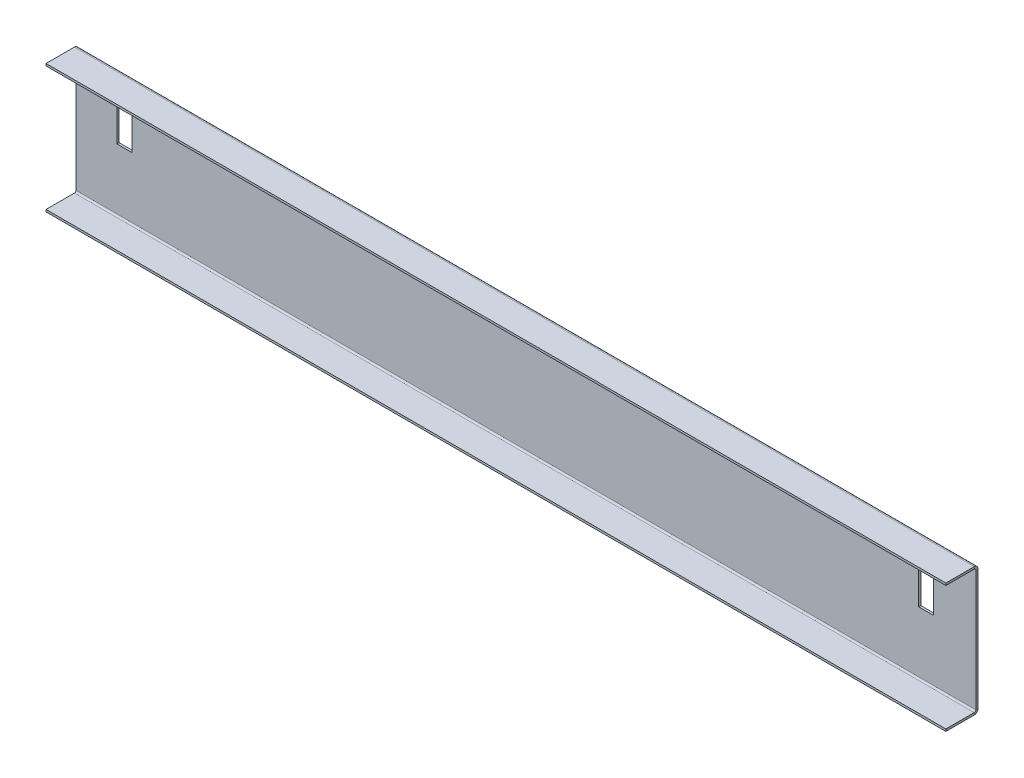
SolidWorks part; units mm, degrees
note: The reader was unsure of these and kept them because the rebuilt part matched: thickness of "Base-Flange1", "Edge-Flange1", "Edge-Flange2", "Sheet-Metal1", "Sheet-Metal2", "Sheet-Metal3", "Sheet-Metal4"; flange length of "Edge-Flange1", "Edge-Flange2".
ref_plane "Front Plane" through (0, 0, 0) normal (0, 0, 1) x (1, 0, 0)
ref_plane "Top Plane" through (0, 0, 0) normal (0, 1, 0) x (1, 0, 0)
ref_plane "Right Plane" through (0, 0, 0) normal (1, 0, 0) x (0, 0, -1)
sketch "Sketch1" plane through (0, 0, 0) normal (0, 0, 1) x (1, 0, 0)
  line L0 (0, 61.3529) -> (0, -66.9118) construction
  line L9 (-200.855, 38.7059) -> (-193.855, 38.7059) construction
  line L10 (-200.855, 38.7059) -> (-200.855, 26.7059) construction
  line L11 (-200.855, 26.7059) -> (-193.855, 26.7059) construction
  line L12 (-193.855, 38.7059) -> (-193.855, 26.7059) construction
  line L13 (-200.855, 38.7059) -> (-193.855, 26.7059) construction
  line L14 (-200.855, 26.7059) -> (-193.855, 38.7059) construction
  line L15 (-200.855, -471.2941) -> (-193.855, -471.2941) construction
  line L16 (-200.855, -471.2941) -> (-200.855, -483.2941) construction
  line L17 (-200.855, -483.2941) -> (-193.855, -483.2941) construction
  line L18 (-193.855, -471.2941) -> (-193.855, -483.2941) construction
  line L19 (-200.855, -471.2941) -> (-193.855, -483.2941) construction
  line L20 (-200.855, -483.2941) -> (-193.855, -471.2941) construction
  line L21 (200.855, -483.2941) -> (193.855, -483.2941) construction
  line L22 (193.855, -471.2941) -> (193.855, -483.2941) construction
  line L23 (200.855, -471.2941) -> (193.855, -471.2941) construction
  line L24 (200.855, -471.2941) -> (200.855, -483.2941) construction
  line L25 (200.855, 26.7059) -> (193.855, 26.7059) construction
  line L26 (193.855, 38.7059) -> (193.855, 26.7059) construction
  line L27 (200.855, 38.7059) -> (193.855, 38.7059) construction
  line L28 (200.855, 38.7059) -> (200.855, 26.7059) construction
  line L29 (-197.355, 38.7059) -> (-197.355, 18.7059) construction
  line L30 (-210, 48.7059) -> (210, 48.7059)
  line L34 (-210, 48.7059) -> (-210, -11.2941)
  line L35 (210, -11.2941) -> (210, 48.7059)
  line L36 (-200.855, 26.7059) -> (-193.855, 26.7059) construction
  line L37 (-200.855, 26.7059) -> (-200.855, 18.7059) construction
  line L38 (-200.855, 18.7059) -> (-193.855, 18.7059) construction
  line L39 (-193.855, 26.7059) -> (-193.855, 18.7059) construction
  line L40 (193.855, 26.7059) -> (200.855, 26.7059) construction
  line L41 (193.855, 26.7059) -> (193.855, 18.7059) construction
  line L42 (193.855, 18.7059) -> (200.855, 18.7059) construction
  line L43 (200.855, 26.7059) -> (200.855, 18.7059) construction
  line L47 (-210, -11.2941) -> (210, -11.2941)
  point P0 (-197.355, 32.7059)
  point P5 (-197.355, -477.2941)
  point P17 (-197.355, 28.7059)
  point P24 (0, 28.7059)
  dimension "D1" = 7
  dimension "D2" = 7
  dimension "D3" = 12
  dimension "D4" = 12
  dimension "D5" = 197.355
  dimension "D6" = 510
  dimension "D7" = 210
  dimension "D8" = 420
  dimension "D9" = 20
  dimension "D10" = 20
  dimension "D11" = 60
  dimension "D12" = 20
base flange "Base-Flange1" sketch "Sketch1" thickness 1 reverse thickness direction no parameters "D1"=0.7366
edge flange "Edge-Flange1" sketch "Sketch8" flange angle 90 flange length 15 flange position material inside bend radius 0.7366 thickness 1 relief rectangular parameters "D6"=10
sketch "Sketch8" plane through (0, 48.7059, 0) normal (0, 1, 0) x (-1, 0, 0)
  line L2 (-210, 0) -> (-210, 14)
  line L3 (-210, 14) -> (210, 14)
  line L4 (210, 14) -> (210, 0)
  line L7 (-210, 0) -> (210, 0) construction
  line L8 (-210, 0) -> (210, 0)
bend "EdgeBend1" bend radius 0.7366 bend angle 90 parameters "D5"=1
edge flange "Edge-Flange2" sketch "Sketch14" flange angle 90 flange length 15 flange position material inside bend radius 0.7366 thickness 1 relief rectangular parameters "D6"=10
bend "EdgeBend3" bend radius 0.7366 bend angle 90 parameters "D5"=2
sketch "Sketch14" plane through (0, -11.2941, 0) normal (0, -1, 0) x (1, 0, 0)
  line L0 (-210, 0) -> (210, 0) construction
  line L1 (-210, 0) -> (210, 0)
  line L2 (-210, 0) -> (-210, 14)
  line L3 (-210, 14) -> (210, 14)
  line L4 (210, 14) -> (210, 0)
sketch "Sketch15" plane through (0, 0, 0) normal (0, 0, 1) x (1, 0, 0)
  line L1 (189.818, 8.75) -> (183.818, 8.75)
  line L2 (189.818, 8.75) -> (189.818, 22.75)
  line L3 (189.818, 22.75) -> (183.818, 22.75)
  line L4 (183.818, 8.75) -> (183.818, 22.75)
sketch "Sketch12" plane through (0, 0, 0) normal (0, 0, 1) x (1, 0, 0)
  line L0 (0, 74.6372) -> (0, -36.0253) construction
  line L1 (-190.855, 38.75) -> (-183.855, 38.75)
  line L2 (-190.855, 38.75) -> (-190.855, 18.75)
  line L4 (-183.855, 38.75) -> (-183.855, 18.75)
  line L9 (-183.855, 28.75) -> (183.855, 28.75) construction
  line L11 (-190.855, 38.75) -> (-190.855, 18.75)
  line L12 (-190.855, 18.75) -> (-183.855, 18.75)
  line L13 (-183.855, 38.75) -> (-183.855, 18.75)
  line L15 (183.318, 38.75) -> (190.318, 38.75)
  line L16 (183.318, 38.75) -> (183.318, 18.75)
  line L17 (183.318, 18.75) -> (190.318, 18.75)
  line L18 (190.318, 38.75) -> (190.318, 18.75)
  line L19 (183.318, 38.75) -> (190.318, 18.75) construction
  line L20 (183.318, 18.75) -> (190.318, 38.75) construction
  point P4 (186.818, 28.75)
  dimension "D1" = 20
  dimension "D2" = 7
  dimension "D3" = 183.855
  dimension "D4" = 20
  dimension "D5" = 18.75
  dimension "D6" = 7
extrude "Cut-Extrude1" cut sketch "Sketch12" against normal through all contours L18 L15 L16 L17 | L2 L12 L4 L1 normal cut yes
sketch "Bend-Lines1" [suppressed] plane through (0, 0, 0) normal (0, 1, 0) x (1, 0, 0)
sketch "Bounding-Box1" [suppressed] plane through (0, 0, 0) normal (0, 1, 0) x (1, 0, 0)
sheet metal parameters "Sheet-Metal1" thickness 1 parameters "D1"=0.7366
flat pattern "Flat-Pattern1" [suppressed]
sketch "Bend-Lines2" plane through (0, 0, 0) normal (0, 1, 0) x (1, 0, 0)
sketch3d "Bounding-Box2" [suppressed]
  line L0 (225, 12.7059, 0) -> (-225, 12.7059, 0) construction
  line L1 (225, 52.7059, 0) -> (-225, 52.7059, 0) construction
  line L2 (225, 12.7059, 0) -> (225, 52.7059, 0) construction
  line L3 (-225, 12.7059, 0) -> (-225, 52.7059, 0) construction
sheet metal parameters "Sheet-Metal2" thickness 1 parameters "D1"=0.7366, "D7"=2
flat pattern "Flat-Pattern1"
sketch "Bend-Lines2" plane through (0, 0, 0) normal (0, 0, 1) x (1, 0, 0)
  line L0 (225, 51.3332) -> (-225, 51.3332) construction
  line L1 (225, 51.3332) -> (-225, 51.3332) construction
sketch3d "Bounding-Box2" [suppressed]
  line L0 (-225, 12.7059, 0) -> (225, 12.7059, 0) construction
  line L1 (-225, 64.9605, 0) -> (225, 64.9605, 0) construction
  line L2 (-225, 12.7059, 0) -> (-225, 64.9605, 0) construction
  line L3 (225, 12.7059, 0) -> (225, 64.9605, 0) construction
bend of the flat pattern "Flatten-<EdgeBend1>1"
sheet metal parameters "Sheet-Metal3" thickness 1 parameters "D1"=0.7366, "D7"=2
flat pattern "Flat-Pattern1" [suppressed]
sketch "Bend-Lines2" plane through (0, 0, 0) normal (0, 0, 1) x (1, 0, 0)
  line L0 (225, 51.3332) -> (-225, 51.3332) construction
  line L1 (225, 51.3332) -> (-225, 51.3332) construction
  line L2 (-225, 14.0786) -> (225, 14.0786) construction
  line L3 (-225, 14.0786) -> (225, 14.0786) construction
sketch3d "Bounding-Box2" [suppressed]
  line L0 (-225, 0.4512, 0) -> (225, 0.4512, 0) construction
  line L1 (-225, 64.9605, 0) -> (225, 64.9605, 0) construction
  line L2 (-225, 0.4512, 0) -> (-225, 64.9605, 0) construction
  line L3 (225, 0.4512, 0) -> (225, 64.9605, 0) construction
bend of the flat pattern "Flatten-<EdgeBend1>1"
bend of the flat pattern "Flatten-<EdgeBend3>1"
sheet metal parameters "Sheet-Metal4" thickness 1 parameters "D1"=0.7366, "D7"=2
flat pattern "Flat-Pattern1"
sketch "Bend-Lines2" plane through (0, 0, 0) normal (0, 0, 1) x (1, 0, 0)
  line L0 (210, 47.9405) -> (-210, 47.9405) construction
  line L1 (210, 47.9405) -> (-210, 47.9405) construction
  line L2 (-210, -10.5287) -> (210, -10.5287) construction
  line L3 (-210, -10.5287) -> (210, -10.5287) construction
sketch3d "Bounding-Box2" [suppressed]
  line L0 (-210, -24.7634, 0) -> (210, -24.7634, 0) construction
  line L1 (-210, 62.1751, 0) -> (210, 62.1751, 0) construction
  line L2 (-210, -24.7634, 0) -> (-210, 62.1751, 0) construction
  line L3 (210, -24.7634, 0) -> (210, 62.1751, 0) construction
bend of the flat pattern "Flatten-<EdgeBend1>1"
bend of the flat pattern "Flatten-<EdgeBend3>2"
sheet metal parameters "Sheet-Metal5" thickness 2 parameters "D1"=0.7366
flat pattern "Flat-Pattern5"
sketch "Bend-Lines3" plane through (0, -11.2941, 0) normal (0, -1, 0) x (-1, 0, 0)
  line L0 (210, 0.6273) -> (-210, 0.6273) construction
  line L1 (210, 0.6273) -> (-210, 0.6273) construction
sketch3d "Bounding-Box3" [suppressed]
  line L0 (-210, -13, 0) -> (210, -13, 0) construction
  line L1 (-210, 1.9912, 0) -> (210, 1.9912, 0) construction
  line L2 (-210, -13, 0) -> (-210, 1.9912, 0) construction
  line L3 (210, -13, 0) -> (210, 1.9912, 0) construction
bend of the flat pattern "Flatten-<EdgeBend3>3"
sheet metal parameters "Sheet-Metal6" thickness 2 parameters "D1"=0.7366
flat pattern "Flat-Pattern6" [suppressed]
sketch "Bend-Lines4" plane through (0, 0, 0) normal (0, 1, 0) x (1, 0, 0)
sketch "Bounding-Box4" [suppressed] plane through (0, 0, 0) normal (0, 1, 0) x (1, 0, 0)
bend of the flat pattern "Flatten-<EdgeBend1>2"
sheet metal parameters "Sheet-Metal7" thickness 2 parameters "D1"=0.7366
flat pattern "Flat-Pattern7"
sketch "Bend-Lines5" plane through (0, 0, 0) normal (0, 1, 0) x (1, 0, 0)
sketch3d "Bounding-Box5" [suppressed]
  line L0 (190.318, 38.75, 0) -> (190.318, 18.75, 0) construction
  line L1 (183.318, 38.75, 0) -> (183.318, 18.75, 0) construction
  line L2 (190.318, 38.75, 0) -> (183.318, 38.75, 0) construction
  line L3 (190.318, 18.75, 0) -> (183.318, 18.75, 0) construction
